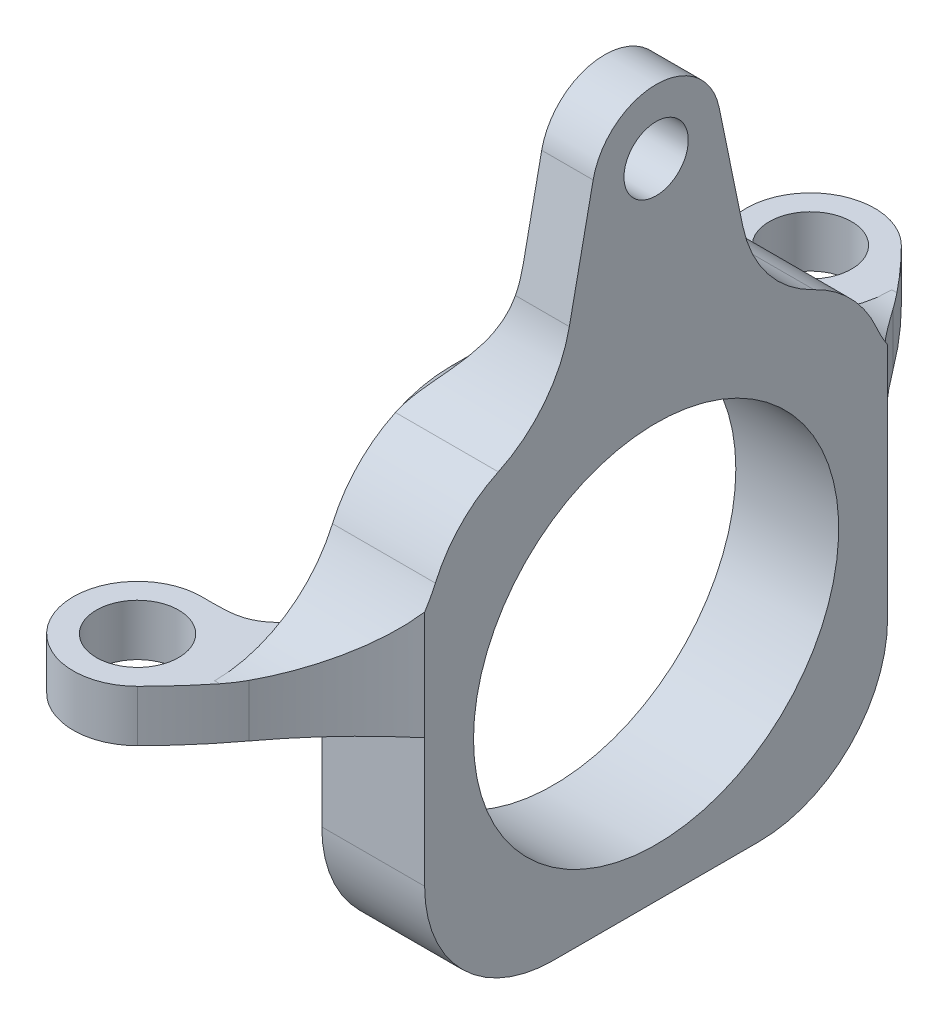
SolidWorks part; units mm, degrees
ref_plane "Front Plane" through (0, 0, 0) normal (0, 0, 1) x (1, 0, 0)
ref_plane "Top Plane" through (0, 0, 0) normal (0, 1, 0) x (1, 0, 0)
ref_plane "Right Plane" through (0, 0, 0) normal (1, 0, 0) x (0, 0, -1)
sketch "Sketch1" plane through (0, 0, 0) normal (0, 1, 0) x (1, 0, 0)
  line L0 (0, 0) -> (14.8492, -14.8492) construction
  line L1 (-13.0815, -13.0815) -> (13.0815, -13.0815) construction
  line L2 (-13.0815, -13.0815) -> (-13.0815, 13.0815) construction
  line L3 (-13.0815, 13.0815) -> (13.0815, 13.0815) construction
  line L4 (13.0815, -13.0815) -> (13.0815, 13.0815) construction
  line L5 (-13.0815, -13.0815) -> (13.0815, 13.0815) construction
  line L6 (-13.0815, 13.0815) -> (13.0815, -13.0815) construction
  line L7 (0, 0) -> (14.8492, 14.8492) construction
  line L8 (0, 0) -> (21, 0) construction
  line L9 (18.9737, -9) -> (20.1632, -9)
  line L10 (20.1632, -9) -> (16.1632, -9) construction
  line L11 (20.1632, -9) -> (20.1632, 9) construction
  line L12 (20.1632, 9) -> (16.1632, 9) construction
  line L13 (16.1632, -9) -> (16.1632, 9) construction
  line L14 (20.1632, -9) -> (16.1632, 9) construction
  line L15 (20.1632, 9) -> (16.1632, -9) construction
  line L16 (20.1632, -9) -> (20.1632, -5.8689)
  line L17 (18.9737, 9) -> (20.1632, 9)
  line L18 (20.1632, 9) -> (20.1632, 5.8689)
  line L19 (16.1632, 9) -> (16.1632, -9)
  circle A0 centre (0, 0) radius 18.5 construction
  circle A1 centre (0, 0) radius 15.5 construction
  circle A2 centre (13.0815, 13.0815) radius 1.6
  circle A3 centre (13.0815, -13.0815) radius 1.6
  circle A5 centre (13.0815, 13.0815) radius 2.5 construction
  circle A6 centre (13.0815, -13.0815) radius 2.5 construction
  circle A7 centre (0, 0) radius 21 construction
  arc A8 (14.7258, 11.1983) -> (14.7258, -11.1983) centre (0, 0) cw construction
  arc A9 (14.7258, 11.1983) -> (14.8492, 14.8492) centre (13.0815, 13.0815) cw
  arc A10 (14.7258, -11.1983) -> (14.8492, -14.8492) centre (13.0815, -13.0815) ccw
  arc A11 (14.7258, 11.1983) -> (16.1632, 9) centre (0, 0) cw
  arc A12 (16.1632, -9) -> (14.7258, -11.1983) centre (0, 0) cw
  arc A13 (14.8492, 14.8492) -> (18.9737, 9) centre (0, 0) cw
  arc A14 (14.8492, -14.8492) -> (18.9737, -9) centre (0, 0) ccw
  arc A15 (20.1632, 5.8689) -> (20.1632, -5.8689) centre (0, 0) cw
  point P18 (14.8492, 14.8492)
  point P19 (14.8492, -14.8492)
  point P20 (20.1632, -5.8689)
  point P21 (18.1632, 0)
  point P32 (20.1632, 5.8689)
  dimension "D1" = 31
  dimension "D2" = 37
  dimension "D3" = 3.2
  dimension "D4" = 3.2
  dimension "D5" = 5
  dimension "D6" = 5
  dimension "D7" = 18
  dimension "D8" = 4
extrude "Boss-Extrude1" add sketch "Sketch1" along normal blind 2 contours A15 L18 L17 A13 A9 A11 L19 A12 A10 A14 L9 L16 A3 A2 region at (17.0696, 0, 0)
sketch "Sketch2" plane through (0, 2, 0) normal (0, 1, 0) x (1, 0, 0)
  line L1 (20.1632, 9) -> (16.1632, 9)
  line L2 (20.1632, 9) -> (20.1632, -9)
  line L3 (20.1632, -9) -> (16.1632, -9)
  line L4 (16.1632, 9) -> (16.1632, -9)
extrude "Boss-Extrude2" add sketch "Sketch2" along normal blind 6 and the other way blind 12
sketch "Sketch3" plane through (20.1632, 0, 0) normal (1, 0, 0) x (0, 0, -1)
  line L0 (-5.8689, 0) -> (5.8689, 0) construction
  circle A0 centre (0, -1) radius 7.1
  dimension "D2" = 14.2
  dimension "D1" = 1
extrude "Cut-Extrude1" cut sketch "Sketch3" against normal blind 5 and the other way blind 5
fillet "Fillet1" radius 5 4 edges at (18.1632, -10, -9) (18.1632, -10, 9) (18.1632, 8, -9) (18.1632, 8, 9)
fillet "Fillet2" radius 21 2 edges at (18.9737, 1, -9) (18.9737, 1, 9)
fillet "Fillet4" radius 5 2 edges at (16.1632, 1, 9) (16.1632, 1, -9)
fillet "Fillet5" radius 10 2 edges at (14.7258, 1, 11.1983) (14.7258, 1, -11.1983)
fillet "Fillet6" radius 2 2 edges at (15.2978, 1, 10.4033) (15.2978, 1, -10.4033)
fillet "Fillet7" radius 5 2 edges at (18.1632, 2, -9) (18.1632, 2, 9)
sketch "Sketch4" plane through (20.1632, 0, 0) normal (1, 0, 0) x (0, 0, -1)
  line L0 (-14.8492, 0) -> (-12.5178, 0) construction
  line L1 (-4, 8) -> (-1.8743, 18.2823) construction
  line L2 (4, 8) -> (1.9868, 17.7381) construction
  line L3 (-4, 8) -> (-2.4482, 15.5061)
  line L4 (-2.4482, 15.5061) -> (2.4482, 15.5061)
  line L5 (2.4482, 15.5061) -> (4, 8)
  line L6 (4, 8) -> (-4, 8)
  circle A0 centre (0, 15) radius 1.25
  circle A1 centre (0, 15) radius 2.5
  line M12 (4, 8) -> (-4, 8)
  dimension "D2" = 2.5
  dimension "D3" = 5
  dimension "D1" = 15
  dimension "D4" = 0
extrude "Boss-Extrude3" add sketch "Sketch4" against normal blind 2 contours L4 A1 A0 | L4 A1 A0 | A1 L3 L5 M12 region at (20.1632, 10.5103, 0) region at (20.1632, 16.4454, 0) region at (20.1632, 15.4478, 1.7956)
fillet "Fillet8" radius 5 2 edges at (19.1632, 8, -4) (19.1632, 8, 4)
fillet "Fillet9" radius 5 3 edges at (18.1632, 7.8788, -5.094) (18.1632, 7.8788, 5.094) (18.1632, 8, 0)
